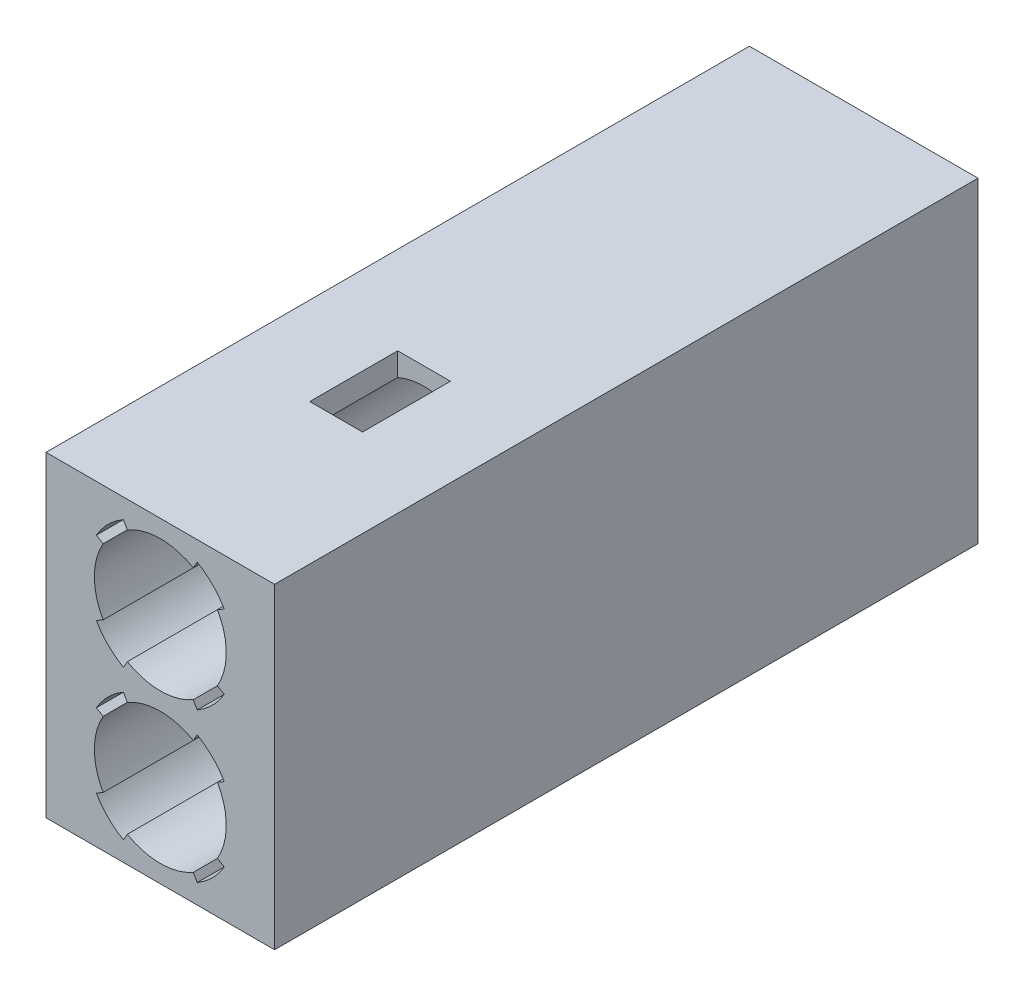
SolidWorks part; units mm, degrees
ref_plane "前基準面" through (0, 0, 0) normal (0, 0, 1) x (1, 0, 0)
ref_plane "上基準面" through (0, 0, 0) normal (0, 1, 0) x (1, 0, 0)
ref_plane "右基準面" through (0, 0, 0) normal (1, 0, 0) x (0, 0, -1)
ref_axis "基準軸1" through (0, -55, 0) along (0, 1, 0)
ref_axis "基準軸2" through (-88.99, 0, 0) along (1, 0, 0)
ref_axis "基準軸3" through (0, 0, 55) along (0, 0, -1)
sketch "草圖1" plane through (0, 0, 0) normal (0, 0, 1) x (1, 0, 0)
  line L1 (-130, 0) -> (0, 0)
  line L2 (-130, 0) -> (-130, 180)
  line L3 (-130, 180) -> (0, 180)
  line L4 (0, 0) -> (0, 180)
  dimension "D1" = 180
  dimension "D2" = 130
extrude "填料-伸長1" add sketch "草圖1" along normal blind 400
sketch "草圖2" plane through (0, 0, 400) normal (0, 0, 1) x (1, 0, 0)
  line L0 (0, 0) -> (0, 180) construction
  line L1 (0, 180) -> (-130, 180) construction
  line L2 (-130, 0) -> (0, 0) construction
  circle A0 centre (-65, 132.5) radius 37.5
  circle A1 centre (-65, 47.5) radius 37.5
  dimension "D4" = 75
  dimension "D5" = 75
  dimension "D1" = 65
  dimension "D2" = 47.5
  dimension "D3" = 47.5
extrude "除料-伸長1" cut sketch "草圖2" against normal through all
ref_plane "平面2" through (0, 0, 5) normal (0, 0, -1) x (-1, 0, 0)
ref_axis "基準軸4" through (-65, 132.5, 0) along (0, 0, 1)
ref_plane "平面1" through (0, 90, 0) normal (0, 1, 0) x (1, 0, 0)
sketch "草圖11" plane through (0, 180, 0) normal (0, 1, 0) x (1, 0, 0)
  line L0 (-65, -400) -> (-65, 46.2584) construction
  line L1 (0, -400) -> (-130, -400) construction
  line L3 (-50, -250) -> (-80, -250)
  line L4 (-50, -250) -> (-50, -300)
  line L6 (-80, -250) -> (-80, -300)
  line L7 (-65, -350) -> (-65, -250) construction
  line L8 (-40, -300) -> (-90, -300) construction
  line L10 (-50, -300) -> (-80, -300)
  point P4 (-65, -300)
  dimension "D1" = 30
  dimension "D2" = 50
  dimension "D3" = 100
  dimension "D4" = 50
extrude "除料-伸長4" cut sketch "草圖11" against normal up to next
sketch "草圖13" plane through (0, 180, 0) normal (0, 1, 0) x (1, 0, 0)
  line L0 (0, -55) -> (0, 55) construction
  line L1 (0, 0) -> (-130, 0) construction
  line L5 (0, -99) -> (0, 99) construction
  line L6 (-76, -54) -> (-54, -54)
  line L7 (-54, -124) -> (-76, -124)
  line L8 (-65, 0) -> (-65, -72) construction
  line L9 (-130, 0) -> (-130, 70) construction
  line L10 (-130, 70) -> (0, 70) construction
  line L11 (0, 70) -> (0, 0) construction
  line L13 (-130, -400) -> (-130, 0) construction
  line L15 (0, 0) -> (-130, 0) construction
  line L16 (-54, -124) -> (-54, -54)
  line L20 (-76, -54) -> (-76, -124)
  line L21 (-65, -83.1553) -> (-65, -60.8447) construction
  circle A1 centre (-65, -11) radius 7 construction
  circle A2 centre (-65, -72) radius 1.1 construction
  point P10 (-65, -18)
  point P23 (-65, -54)
  dimension "D2" = 22
  dimension "D3" = 14
  dimension "D6" = 2.2
  dimension "D1" = 70
  dimension "D4" = 18
  dimension "D5" = 54
  dimension "D7" = 70
  dimension "D8" = 18
sketch "草圖14" plane through (0, 180, 0) normal (0, 1, 0) x (1, 0, 0)
  line L0 (-130, -400) -> (-130, 0) construction
  line L1 (-130, -250) -> (0, -250)
  line L2 (-130, -250) -> (-130, -240)
  line L3 (-130, -240) -> (0, -240)
  line L4 (0, -250) -> (0, -240)
  line L5 (0, -400) -> (0, 0) construction
  line L6 (-50, -250) -> (-80, -250) construction
  dimension "D1" = 10
sketch "草圖17" plane through (0, 0, 400) normal (0, 0, 1) x (1, 0, 0)
  line L2 (-65, 132.5) -> (-65, 47.5) construction
  line L3 (16.636, 90) -> (-161.4893, 90) construction
  line L4 (-44, 83.8731) -> (-46.5, 79.5429)
  line L5 (-28.6269, 68.5) -> (-32.9571, 66)
  line L6 (-44, 168.8731) -> (-46.5, 164.5429)
  line L7 (-28.6269, 153.5) -> (-32.9571, 151)
  line L8 (-28.6269, 111.5) -> (-32.9571, 114)
  line L9 (-44, 96.1269) -> (-46.5, 100.4571)
  line L10 (-86, 96.1269) -> (-83.5, 100.4571)
  line L11 (-101.3731, 111.5) -> (-97.0429, 114)
  line L12 (-101.3731, 153.5) -> (-97.0429, 151)
  line L13 (-86, 168.8731) -> (-83.5, 164.5429)
  line L14 (-28.6269, 26.5) -> (-32.9571, 29)
  line L15 (-44, 11.1269) -> (-46.5, 15.4571)
  line L16 (-86, 11.1269) -> (-83.5, 15.4571)
  line L17 (-101.3731, 26.5) -> (-97.0429, 29)
  line L18 (-101.3731, 68.5) -> (-97.0429, 66)
  line L19 (-86, 83.8731) -> (-83.5, 79.5429)
  circle A2 centre (-65, 132.5) radius 37.5 construction
  circle A3 centre (-65, 132.5) radius 37.5 construction
  circle A4 centre (-65, 47.5) radius 37.5 construction
  circle A5 centre (-65, 47.5) radius 37.5 construction
  arc A6 (-32.9571, 66) -> (-46.5, 79.5429) centre (-65, 47.5) ccw
  arc A7 (-28.6269, 68.5) -> (-44, 83.8731) centre (-65, 47.5) ccw
  arc A8 (-32.9571, 151) -> (-46.5, 164.5429) centre (-65, 132.5) ccw
  arc A9 (-28.6269, 153.5) -> (-44, 168.8731) centre (-65, 132.5) ccw
  arc A10 (-46.5, 100.4571) -> (-32.9571, 114) centre (-65, 132.5) ccw
  arc A11 (-44, 96.1269) -> (-28.6269, 111.5) centre (-65, 132.5) ccw
  arc A12 (-97.0429, 114) -> (-83.5, 100.4571) centre (-65, 132.5) ccw
  arc A13 (-101.3731, 111.5) -> (-86, 96.1269) centre (-65, 132.5) ccw
  arc A14 (-83.5, 164.5429) -> (-97.0429, 151) centre (-65, 132.5) ccw
  arc A15 (-86, 168.8731) -> (-101.3731, 153.5) centre (-65, 132.5) ccw
  arc A16 (-46.5, 15.4571) -> (-32.9571, 29) centre (-65, 47.5) ccw
  arc A17 (-44, 11.1269) -> (-28.6269, 26.5) centre (-65, 47.5) ccw
  arc A18 (-97.0429, 29) -> (-83.5, 15.4571) centre (-65, 47.5) ccw
  arc A19 (-101.3731, 26.5) -> (-86, 11.1269) centre (-65, 47.5) ccw
  arc A20 (-83.5, 79.5429) -> (-97.0429, 66) centre (-65, 47.5) ccw
  arc A21 (-86, 83.8731) -> (-101.3731, 68.5) centre (-65, 47.5) ccw
  point P9 (-65, 90)
  point P32 (-65, 132.5)
  point P45 (-65, 47.5)
  dimension "D3" = 30
  dimension "D4" = 37
  dimension "D7" = 30
  dimension "D10" = 42
  dimension "D11" = 37
  dimension "D5" = 42
  dimension "D6" = 5
  dimension "D9" = 5
  dimension "D12" = 60
  dimension "D13" = 60
  dimension "D2" = 30
  dimension "D8" = 30
  dimension "D14" = 4
  dimension "D15" = 4
extrude "除料-伸長9" cut sketch "草圖17" against normal through all
sketch "草圖18" plane through (-130, 0, 0) normal (-1, 0, 0) x (0, 0, 1)
  line L0 (0, 90) -> (400, 90) construction
  line L1 (0, 180) -> (0, 0) construction
  line L2 (400, 180) -> (400, 0) construction
  line L3 (400, 0) -> (0, 0) construction
  line L4 (400, 180) -> (0, 180) construction
  line L6 (70, 98) -> (0, 98)
  line L7 (70, 98) -> (70, 82)
  line L8 (70, 82) -> (0, 82)
  line L9 (0, 98) -> (0, 82)
  line L10 (35, 82) -> (35, 98) construction
  line L11 (70, 90) -> (0, 90) construction
  circle A0 centre (12.5, 90) radius 1.5 construction
  circle A1 centre (57.5, 90) radius 1.5 construction
  point P14 (35, 90)
  dimension "D3" = 45
  dimension "D4" = 3
  dimension "D1" = 90
  dimension "D2" = 90
  dimension "D5" = 12.5
  dimension "D6" = 16
  dimension "D7" = 70
ref_plane "平面3" through (-65, 0, 0) normal (1, 0, 0) x (0, 0, -1)
